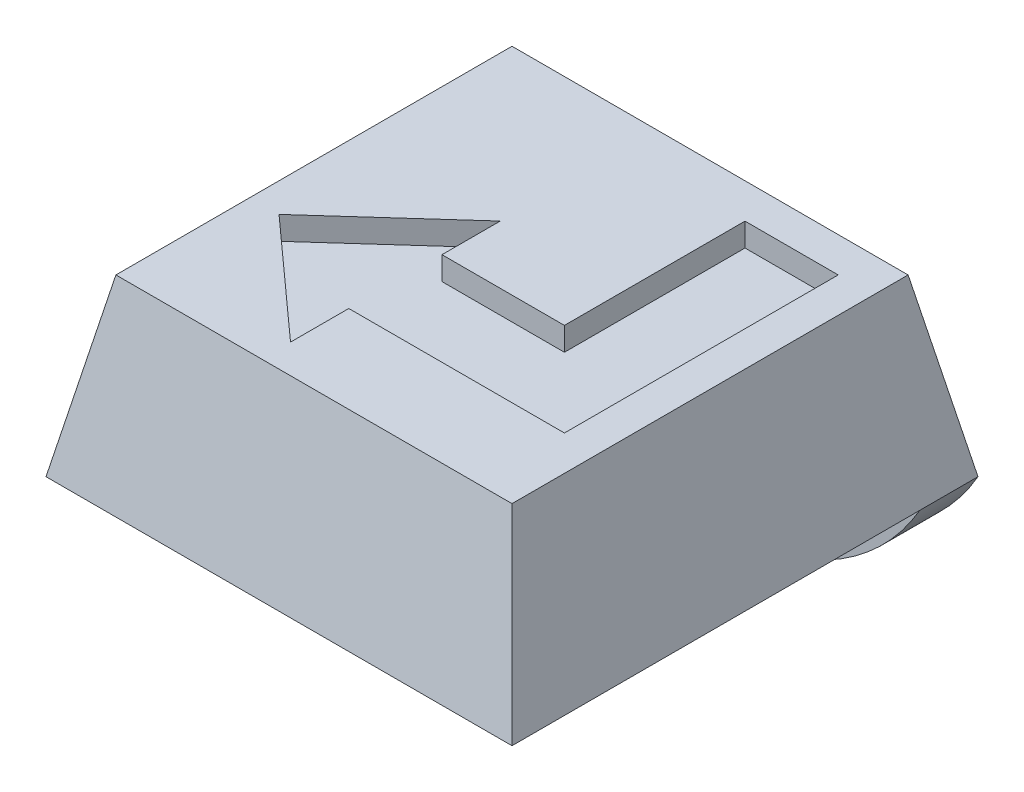
SolidWorks part; units mm, degrees
ref_plane "Front Plane" through (0, 0, 0) normal (0, 0, 1) x (1, 0, 0)
ref_plane "Top Plane" through (0, 0, 0) normal (0, 1, 0) x (1, 0, 0)
ref_plane "Right Plane" through (0, 0, 0) normal (1, 0, 0) x (0, 0, -1)
sketch "Sketch1" plane through (0, 0, 0) normal (0, 1, 0) x (1, 0, 0)
  line L1 (0, 0) -> (8, 0)
  line L2 (0, 0) -> (0, 8)
  line L3 (0, 8) -> (8, 8)
  line L4 (8, 0) -> (8, 8)
  dimension "D1" = 8
  dimension "D2" = 8
extrude "Boss-Extrude1" add sketch "Sketch1" along normal blind 3
sketch "Sketch2" plane through (0, 0, 0) normal (0, 0, 1) x (1, 0, 0)
  line L0 (0, 0) -> (0.6, 3)
  line L1 (0, 3) -> (8, 3) construction
  line L2 (0.6, 3) -> (0, 3)
  line L3 (0, 3) -> (0, 0)
  line L4 (8, 0) -> (7.4, 3)
  line L5 (7.4, 3) -> (8, 3)
  line L6 (8, 3) -> (8, 0)
  dimension "D1" = 0.6
  dimension "D2" = 0.6
extrude "Cut-Extrude1" cut sketch "Sketch2" against normal through all both and the other way through all
sketch "Sketch3" plane through (0, 0, 0) normal (1, 0, 0) x (0, 0, -1)
  line L0 (0, 0) -> (0.6, 3)
  line L1 (8, 3) -> (0, 3) construction
  line L2 (0.6, 3) -> (0, 3)
  line L3 (0, 3) -> (0, 0)
  line L4 (8, 3) -> (7.4, 3)
  line L5 (7.4, 3) -> (8, 0)
  line L6 (8, 3) -> (8, 0)
  dimension "D1" = 0.6
  dimension "D2" = 0.6
extrude "Cut-Extrude2" cut sketch "Sketch3" along normal blind 11
sketch "Sketch4" plane through (0, 0, 0) normal (0, -1, 0) x (1, 0, 0)
  line L0 (8, 0) -> (8, -8) construction
  line L3 (0, 0) -> (8, 0) construction
  circle A0 centre (4, -3.75) radius 1.8
  dimension "D1" = 3.6
  dimension "D2" = 4
  dimension "D3" = 3.75
extrude "Cut-Extrude3" cut sketch "Sketch4" against normal blind 0.8
sketch "Sketch5" plane through (0, 0, 0) normal (0, -1, 0) x (1, 0, 0)
  line L0 (8, 0) -> (8, -8) construction
  line L1 (0, -8) -> (8, -8)
  line L2 (0, -8) -> (0, -7)
  line L3 (0, -7) -> (8, -7)
  line L4 (8, -8) -> (8, -7)
  dimension "D1" = 1
extrude "Boss-Extrude2" add sketch "Sketch5" along normal blind 2
fillet "Fillet1" radius 4 2 edges at (8, -2, -7.5) (0, -2, -7.5)
sketch "Sketch6" plane through (0, 3, 0) normal (0, 1, 0) x (1, 0, 0)
  line L0 (3.0978, 3.7) -> (3.0978, 4.7)
  line L1 (5.2, 6.8) -> (6.8, 6.8)
  line L2 (5.2, 6.8) -> (5.2, 2.1)
  line L3 (5.2, 2.1) -> (6.8, 2.1)
  line L4 (6.8, 6.8) -> (6.8, 2.1)
  line L5 (5.2, 2.1) -> (3.0978, 2.1)
  line L6 (5.2, 2.1) -> (5.2, 3.7)
  line L7 (5.2, 3.7) -> (3.0978, 3.7)
  line L8 (3.0978, 2.1) -> (3.0978, 3.7)
  line L9 (3.0978, 4.7) -> (1.1, 2.9)
  line L10 (1.1, 2.9) -> (3.0978, 1.1)
  line L11 (3.0978, 1.1) -> (3.0978, 2.1)
  line L12 (7.4, 7.4) -> (7.4, 0.6) construction
  line L13 (7.4, 7.4) -> (0.6, 7.4) construction
  line L14 (7.4, 0.6) -> (0.6, 0.6) construction
  line L15 (0.6, 7.4) -> (0.6, 0.6) construction
  point P16 (1.2781, 3.6607)
  point P19 (3.0978, 2.9)
  dimension "D1" = 0.6
  dimension "D2" = 0.6
  dimension "D3" = 0.5
  dimension "D4" = 1
  dimension "D5" = 1
  dimension "D6" = 1.6
  dimension "D7" = 1.6
  dimension "D8" = 0.5
  dimension "D9" = 0
extrude "Cut-Extrude4" cut sketch "Sketch6" against normal blind 0.4 contours L10 L11 L8 L0 L9 | L8 L5 L2 L7 | L2 L1 L4 L3 region at (2.4319, 3, -2.9) region at (4.1489, 3, -2.9)
